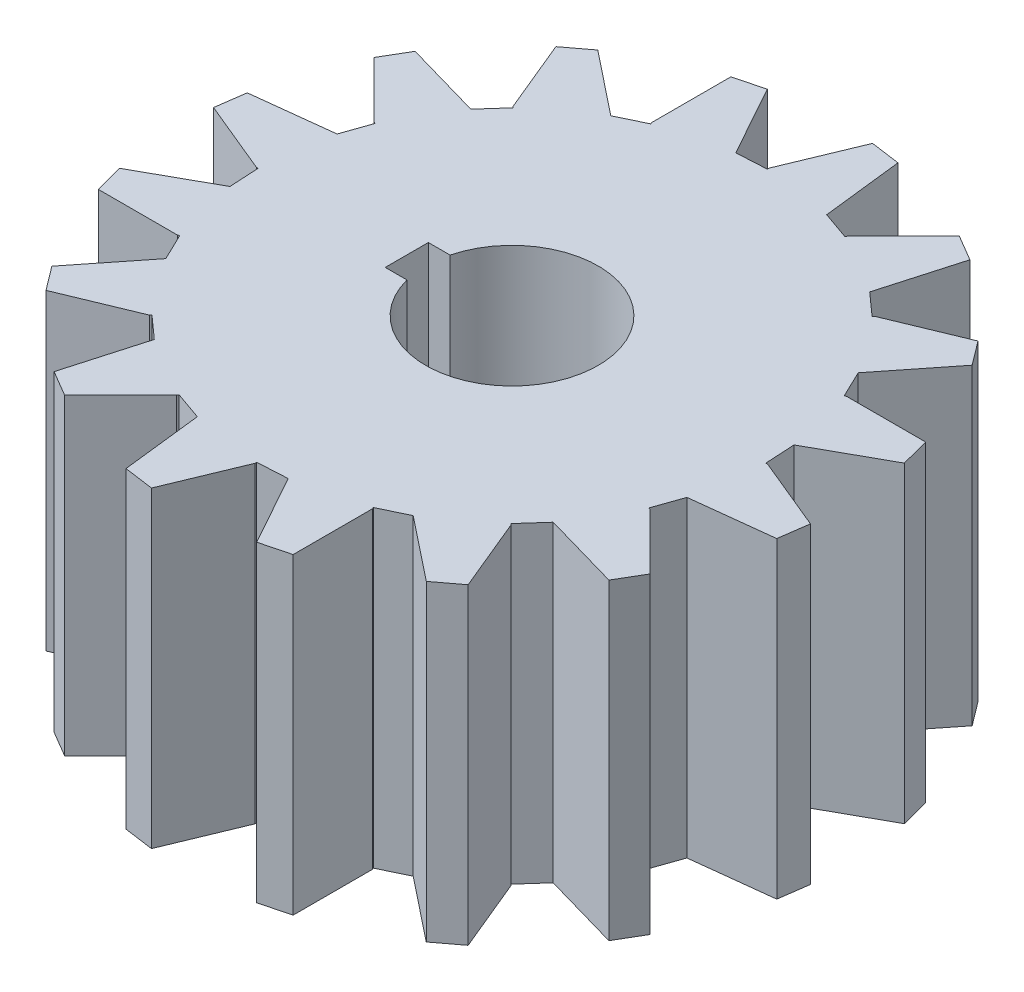
SolidWorks part; units mm, degrees
ref_plane "Plan de face" through (0, 0, 0) normal (0, 0, 1) x (1, 0, 0)
ref_plane "Plan de dessus" through (0, 0, 0) normal (0, 1, 0) x (1, 0, 0)
ref_plane "Plan de droite" through (0, 0, 0) normal (1, 0, 0) x (0, 0, -1)
sketch "Esquisse1" plane through (0, 0, 0) normal (0, 0, 1) x (1, 0, 0)
  line L0 (-198.5, 46) -> (-198.5, 0)
  line L1 (-150, 46) -> (0, 46)
  line L2 (0, 46) -> (0, 0)
  line L3 (0, 46) -> (0, 0) construction
  line L4 (0, 0) -> (-150, 0)
  line L18 (-198.5, 46) -> (-150, 46)
  line L19 (-150, 46) -> (-150, 0) construction
  line L20 (-150, 0) -> (-198.5, 0)
  dimension "D2" = 46
  dimension "D3" = 198.5
  dimension "D15" = 150
revolve "Révolution1" add sketch "Esquisse1" angle 360 about L3
sketch "Esquisse5" plane through (0, 46, 0) normal (0, 1, 0) x (1, 0, 0)
  line L0 (-37.5, 0) -> (0, 0) construction
  line L1 (-36.0593, 10.2944) -> (-46.6706, 13.3238) construction
  line L2 (-46.6706, 13.3238) -> (-47.9254, 8.9285) construction
  line L3 (-37.5, 0) -> (-48.75, 0)
  line L4 (-34.6053, 14.4473) -> (-44.9869, 18.7814)
  line L5 (-44.9869, 18.7814) -> (-183.1774, 76.4741)
  line L6 (-34.6053, 14.4473) -> (-36.0593, 10.2944)
  line L7 (-36.0593, 10.2944) -> (-47.9254, 8.9285)
  line L8 (-47.9254, 8.9285) -> (-48.5352, 4.5709)
  line L9 (-48.5352, 4.5709) -> (-37.5, 0)
  line L10 (-34.6053, 14.4473) -> (0, 0) construction
  line L13 (-48.75, 0) -> (-198.5, 0)
  line L14 (-183.1774, 76.4741) -> (-202.6005, 84.583)
  line L15 (-198.5, 0) -> (-207.9616, 0)
  line L16 (-207.9616, 0) -> (-202.6005, 84.583)
  circle A0 centre (0, 0) radius 48.75 construction
  circle A1 centre (0, 0) radius 37.5 construction
  circle A2 centre (0, 0) radius 40 construction
  circle A3 centre (0, 0) radius 198.5 construction
  point P8 (-37.5, 0)
  point P9 (-34.6053, 14.4473)
  circle M36 centre (0, 0) radius 198.5
  dimension "D1" = 80
  dimension "D2" = 2.5
  dimension "D3" = 11.25
  dimension "D4" = 4.4
  dimension "D5" = 4.4
  dimension "D6" = 22.5
  dimension "D7" = 22.5
extrude "Enlèv. mat.-Extru.3" cut sketch "Esquisse5" against normal through all contours L13 L3 L9 L8 L7 L6 L4 L5 M36 | L16 L15 L14 M36 region at (-133.7933, 46, -26.8357) region at (-198.5362, 46, -46.5619)
ref_axis "Axe1" through (0, 39.3, 0) along (0, -1, 0)
pattern_circular "Répétition circulaire1" count 16 over 360 about axis through (0, 39.3, 0) along (0, -1, 0) of "Enlèv. mat.-Extru.3"
sketch "Esquisse6" plane through (0, 46, 0) normal (0, 1, 0) x (1, 0, 0)
  line L0 (0, 0) -> (-12.7, 0) construction
  line L1 (-12.2967, 3.175) -> (-15.4967, 3.175)
  line L2 (-15.4967, 3.175) -> (-15.4967, -3.175)
  line L3 (-15.4967, -3.175) -> (-12.2967, -3.175)
  line L4 (-12.7, 0) -> (-15.4967, 0) construction
  circle A0 centre (0, 0) radius 12.7 construction
  arc A1 (-12.2967, 3.175) -> (-12.2967, -3.175) centre (0, 0) cw
  dimension "D3" = 25.4
  dimension "D1" = 6.35
  dimension "D2" = 3.2
extrude "Enlèv. mat.-Extru.4" cut sketch "Esquisse6" against normal through all
